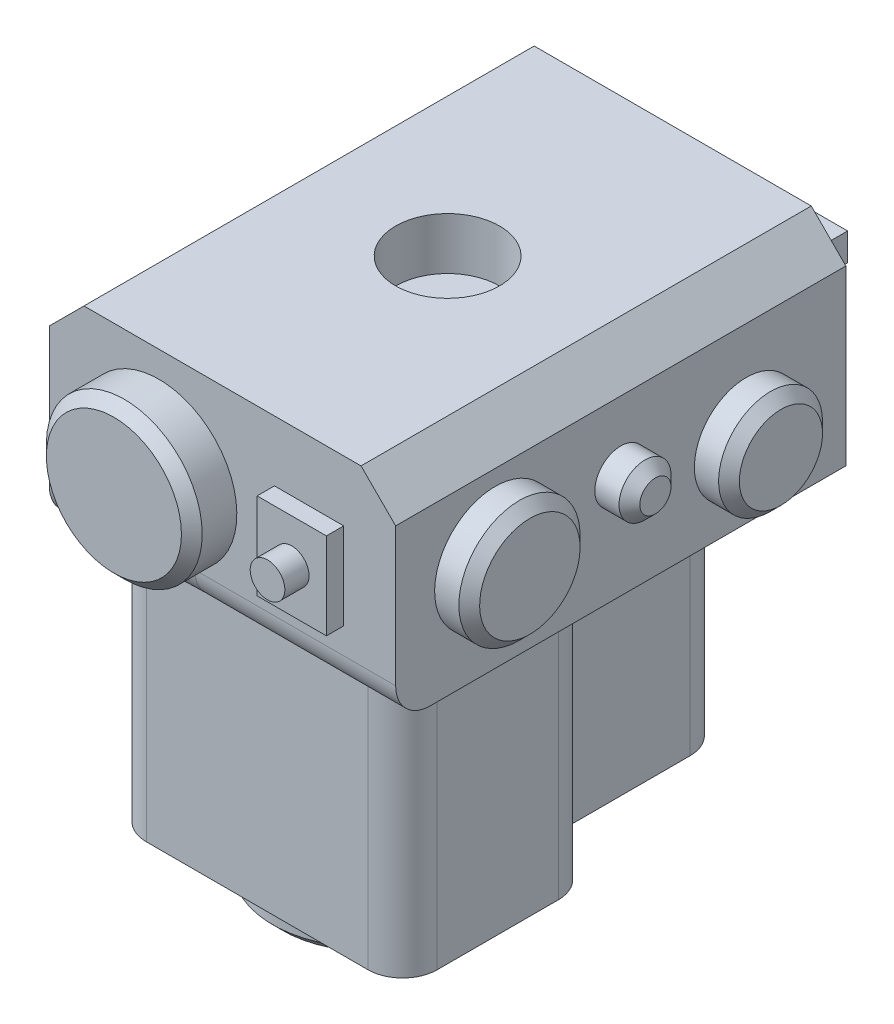
SolidWorks part; units mm, degrees
ref_plane "Ön Düzlem" through (0, 0, 0) normal (0, 0, 1) x (1, 0, 0)
ref_plane "Üst Düzlem" through (0, 0, 0) normal (0, 1, 0) x (1, 0, 0)
ref_plane "Sağ Düzlem" through (0, 0, 0) normal (1, 0, 0) x (0, 0, -1)
sketch "Sketch1" plane through (0, 0, 0) normal (0, 0, 1) x (1, 0, 0)
  line L0 (-40, 30) -> (-50, 20)
  line L1 (40, 30) -> (-40, 30)
  line L2 (50, 20) -> (50, -30)
  line L3 (50, -30) -> (-50, -30)
  line L4 (-50, 20) -> (-50, -30)
  line L5 (50, 30) -> (-50, -30) construction
  line L6 (50, -30) -> (-50, 30) construction
  line L7 (50, 20) -> (40, 30)
  point P0 (0, 0)
  dimension "D1" = 60
  dimension "D2" = 100
extrude "Boss-Extrude1" add sketch "Sketch1" along normal mid plane 130
sketch "Sketch2" plane through (0, -30, 0) normal (0, -1, 0) x (1, 0, 0)
  line L0 (0, -55) -> (0, 55) construction
  line L1 (42, 55) -> (-42, 55)
  line L2 (-42, 55) -> (-42, 0)
  line L3 (-42, 0) -> (-25, 0)
  line L4 (-25, 0) -> (-25, -55)
  line L5 (-25, -55) -> (25, -55)
  line L6 (-25, 0) -> (0, 0) construction
  line L7 (25, 0) -> (25, -55)
  line L8 (42, 0) -> (25, 0)
  line L9 (42, 55) -> (42, 0)
  dimension "D1" = 25
  dimension "D2" = 42
  dimension "D3" = 110
extrude "Boss-Extrude2" add sketch "Sketch2" along normal blind 75
sketch "Sketch3" plane through (0, -105, 0) normal (0, -1, 0) x (1, 0, 0)
  circle A0 centre (0, 23) radius 27.5
  dimension "D1" = 55
  dimension "D2" = 23
extrude "Boss-Extrude3" add sketch "Sketch3" along normal blind 10 contours A0
sketch "Sketch4" plane through (0, -115, 0) normal (0, -1, 0) x (1, 0, 0)
  circle A0 centre (0, 23) radius 5
  dimension "D1" = 10
extrude "Cut-Extrude1" cut sketch "Sketch4" against normal blind 2
sketch "Sketch5" plane through (0, 30, 0) normal (0, 1, 0) x (1, 0, 0)
  circle A0 centre (0, 0) radius 15
  dimension "D1" = 30
extrude "Cut-Extrude2" cut sketch "Sketch5" against normal blind 15
sketch "Sketch6" plane through (50, 0, 0) normal (1, 0, 0) x (0, 0, -1)
  line L0 (-65, 20) -> (65, 20) construction
  line L1 (0, 7.5) -> (0, -7.5) construction
  circle A0 centre (0, 0) radius 7.5
  circle A1 centre (-36.25, -2) radius 17.5
  circle A2 centre (36.25, -8.5) radius 15
  dimension "D1" = 15
  dimension "D4" = 35
  dimension "D5" = 30
  dimension "D2" = 8.5
  dimension "D3" = 22
  dimension "D6" = 72.5
  dimension "D7" = 36.25
extrude "Boss-Extrude4" add sketch "Sketch6" along normal blind 10
sketch "Sketch7" plane through (0, 0, 65) normal (0, 0, 1) x (1, 0, 0)
  circle A0 centre (-18.36, 0) radius 22.5
  dimension "D1" = 45
  dimension "D2" = 18.36
extrude "Boss-Extrude5" add sketch "Sketch7" along normal blind 13
sketch "Sketch8" plane through (0, 0, 65) normal (0, 0, 1) x (1, 0, 0)
  line L0 (0, 0) -> (50, 0) construction
  line L1 (50, -19.5) -> (50, 15.5) construction
  line L3 (35, 12.5) -> (15, 12.5)
  line L4 (35, 12.5) -> (35, -12.5)
  line L5 (35, -12.5) -> (15, -12.5)
  line L6 (15, 12.5) -> (15, -12.5)
  line L7 (35, 12.5) -> (15, -12.5) construction
  line L8 (35, -12.5) -> (15, 12.5) construction
  point P5 (25, 0)
  dimension "D1" = 20
  dimension "D2" = 25
  dimension "D3" = 25
extrude "Boss-Extrude6" add sketch "Sketch8" along normal blind 5
sketch "Sketch9" plane through (0, 0, 70) normal (0, 0, 1) x (1, 0, 0)
  line L0 (35, 12.5) -> (15, 12.5) construction
  circle A0 centre (25, 0) radius 5
  point P4 (25, 12.5)
  dimension "D1" = 10
extrude "Boss-Extrude7" add sketch "Sketch9" along normal blind 7
sketch "Sketch10" plane through (0, 0, -65) normal (0, 0, -1) x (-1, 0, 0)
  line L0 (-33, 11) -> (-40.5, 11)
  line L1 (-5.5, 19) -> (-40.5, 19)
  line L2 (-5.5, 19) -> (-5.5, 11)
  line L3 (-5.5, 11) -> (-13, 11)
  line L4 (-40.5, 19) -> (-40.5, 11)
  line L5 (-5.5, 19) -> (-40.5, 11) construction
  line L6 (-5.5, 11) -> (-40.5, 19) construction
  line L7 (-23, 13.9447) -> (-23, 15) construction
  line L8 (-23, 15) -> (-23, 1) construction
  line L9 (-50, -30) -> (-50, 20) construction
  arc A0 (-33, 11) -> (-13, 11) centre (-23, 11) ccw
  point P0 (-23, 15)
  dimension "D3" = 10
  dimension "D1" = 8
  dimension "D2" = 35
  dimension "D4" = 27
  dimension "D5" = 15
  dimension "D6" = 20
extrude "Boss-Extrude8" add sketch "Sketch10" along normal blind 10
chamfer "Chamfer1" distance 3 angle 45 5 edges at (4.14, 0, 78) (27.5, -115, 23) (60, 6.5, -36.25) (60, 7.5, 0) (60, 15.5, 36.25)
fillet "Fillet2" radius 10 7 edges at (42, -67.5, 55) (42, -67.5, 0) (25, -67.5, -55) (-25, -67.5, -55) (-42, -67.5, 0) (-42, -67.5, 55) (0, -30, 65)
